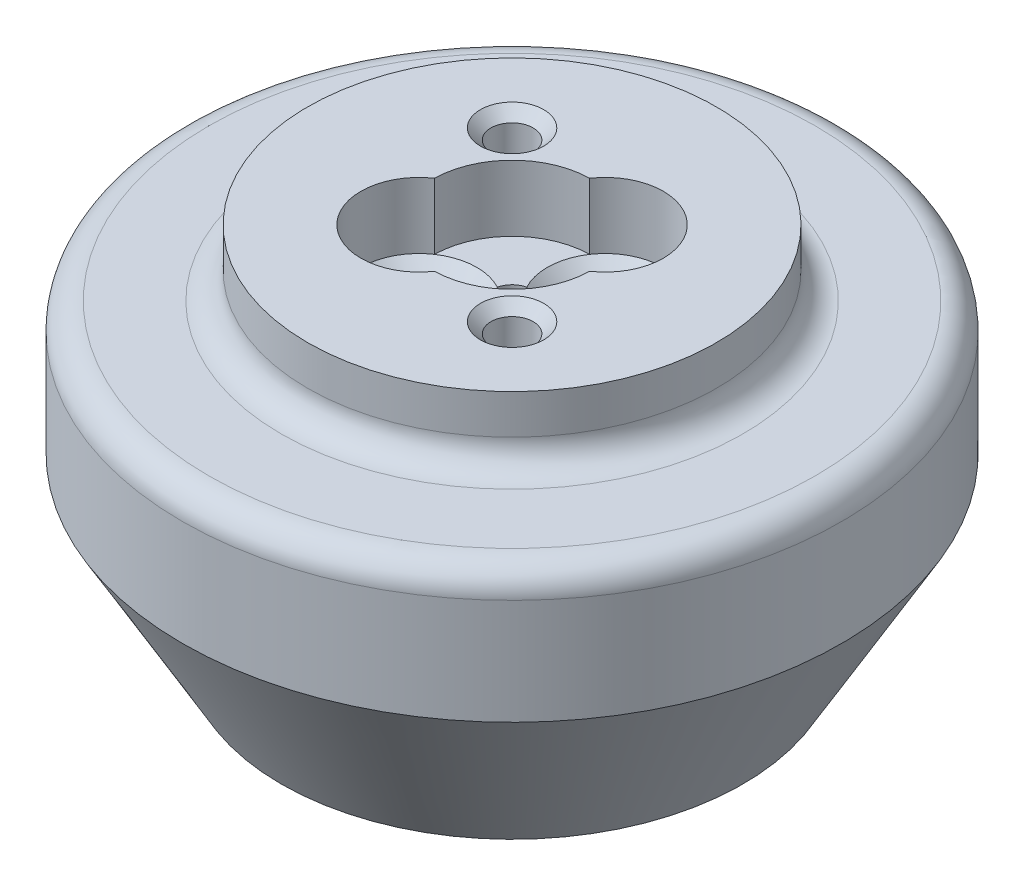
SolidWorks part; units mm, degrees
material "Brass"
ref_plane "Front" through (0, 0, 0) normal (0, 0, 1) x (1, 0, 0)
ref_plane "Top" through (0, 0, 0) normal (0, 1, 0) x (1, 0, 0)
ref_plane "Right" through (0, 0, 0) normal (1, 0, 0) x (0, 0, -1)
sketch "Sketch1" plane through (0, 0, 0) normal (0, 1, 0) x (1, 0, 0)
  circle A0 centre (0, 0) radius 7.1438
  circle A1 centre (0, 0) radius 12.5
  dimension "D1" = 14.2875
  dimension "D2" = 25
extrude "Boss-Extrude1" add sketch "Sketch1" along normal blind 10
sketch "Sketch2" plane through (0, 10, 0) normal (0, 1, 0) x (1, 0, 0)
  circle A0 centre (0, 0) radius 12.5 construction
  circle A1 centre (0, 0) radius 12.5
extrude "Boss-Extrude2" add sketch "Sketch2" along normal blind 1.5
chamfer "Chamfer1" distance 3.75 angle 60 1 edges at (0, 0, 12.5) first distance on face at (0, 0, 12.5)
sketch "Sketch8" plane through (0, 11.5, 0) normal (0, 1, 0) x (1, 0, 0)
  circle A1 centre (0, 0) radius 7.75
  circle A2 centre (0, 0) radius 3
  dimension "D1" = 6
  dimension "D2" = 15.5
extrude "Boss-Extrude3" add sketch "Sketch8" along normal blind 2.5
sketch "Sketch9" plane through (0, 11.5, 0) normal (0, 1, 0) x (1, 0, 0)
  circle A0 centre (1.7678, 1.7678) radius 0.7 construction
  circle A2 centre (-1.7678, -1.7678) radius 0.7 construction
  circle A4 centre (1.7678, 1.7678) radius 0.7 construction
  circle A6 centre (-1.7678, -1.7678) radius 0.7 construction
hole_wizard "CSK for M2 Flat Head Machine Screw1" positions "3DSketch2" profile "Sketch11" countersink size "M2" standard "ANSI Metric" end condition through all
sketch3d "3DSketch2"
  point P0 (-1.7678, 11.5, 1.7678)
  point P6 (1.7678, 11.5, -1.7678)
sketch "Sketch11" plane through (-1.7678, 11.5, 1.7678) normal (1, 0, 0) x (0, 0, 1)
  line L0 (0, 0) -> (0, 11.5)
  line L1 (0, 11.5) -> (1.2, 11.5)
  line L2 (1.2, 11.5) -> (1.2, 1)
  line L3 (1.2, 1) -> (2.2, 0)
  line L5 (2.2, 0) -> (0, 0)
  line L6 (-1.2, 1) -> (-2.2, 0) construction
  line L11 (0, -6.35) -> (0, 107.95) construction
  dimension "Thru Hole Dia." = 2.4
  dimension "Thru Hole Depth" = 11.5
  dimension "Near C'Sink Dia." = 4.4
  dimension "Near C'Sink Angle" = 90
sketch "Sketch16" plane through (0, 11.5, 0) normal (0, 1, 0) x (1, 0, 0)
  circle A0 centre (0, 0) radius 0.75
  dimension "D1" = 1.5
extrude "Cut-Extrude1" cut sketch "Sketch16" against normal through all
sketch "Sketch17" plane through (0, 14, 0) normal (0, 1, 0) x (1, 0, 0)
  circle A0 centre (3.182, -3.182) radius 0.7 construction
  circle A1 centre (-3.182, 3.182) radius 0.7 construction
  circle A2 centre (3.182, -3.182) radius 0.7
  circle A3 centre (-3.182, 3.182) radius 0.7
hole_wizard "M2x0.4 Tapped Hole1" positions "3DSketch4" profile "Sketch19" tap size "M2x0.4" standard "ANSI Metric" end condition through all
sketch3d "3DSketch4"
  point P0 (3.182, 14, 3.182)
  point P3 (-3.182, 14, -3.182)
sketch "Sketch19" plane through (3.182, 14, 3.182) normal (1, 0, 0) x (0, 0, 1)
  line L0 (0, 0) -> (0, 14)
  line L1 (0, 14) -> (0.8, 14)
  line L2 (0.8, 14) -> (0.8, 0.4)
  line L3 (0.8, 0.4) -> (1.2, 0)
  line L5 (1.2, 0) -> (0, 0)
  line L6 (-0.8, 0.4) -> (-1.2, 0) construction
  line L11 (0, -6.35) -> (0, 107.95) construction
  dimension "Thru Tap Drill Dia." = 1.6
  dimension "Thru Tap Drill Depth" = 14
  dimension "Near C'Sink Dia." = 2.4
  dimension "Near C'Sink Angle" = 90
cosmetic thread "Hole Thread3" parameters "D2"=2
cosmetic thread "Hole Thread4" parameters "D2"=2
sketch "Sketch20" plane through (0, 14, 0) normal (0, 1, 0) x (1, 0, 0)
  arc A4 (0.0551, -2.9995) -> (0.1721, -0.73) centre (-1.7678, -1.7678) ccw
  arc A5 (-0.73, 0.1721) -> (0.1721, -0.73) centre (0, 0) ccw
  arc A6 (-0.73, 0.1721) -> (-2.9995, 0.0551) centre (-1.7678, -1.7678) ccw
  arc A7 (-2.9995, 0.0551) -> (0.0551, -2.9995) centre (-1.7678, -1.7678) ccw
  arc A8 (0.0551, -2.9995) -> (0.1721, -0.73) centre (-1.7678, -1.7678) ccw
  arc A9 (-0.73, 0.1721) -> (0.1721, -0.73) centre (0, 0) ccw
  arc A10 (-0.73, 0.1721) -> (-2.9995, 0.0551) centre (-1.7678, -1.7678) ccw
  arc A11 (-2.9995, 0.0551) -> (0.0551, -2.9995) centre (-1.7678, -1.7678) ccw
  arc A12 (-0.0551, 2.9995) -> (-0.1721, 0.73) centre (1.7678, 1.7678) ccw
  arc A13 (0.73, -0.1721) -> (-0.1721, 0.73) centre (0, 0) ccw
  arc A14 (0.73, -0.1721) -> (2.9995, -0.0551) centre (1.7678, 1.7678) ccw
  arc A15 (2.9995, -0.0551) -> (-0.0551, 2.9995) centre (1.7678, 1.7678) ccw
  arc A16 (-0.0551, 2.9995) -> (-0.1721, 0.73) centre (1.7678, 1.7678) ccw
  arc A17 (0.73, -0.1721) -> (-0.1721, 0.73) centre (0, 0) ccw
  arc A18 (0.73, -0.1721) -> (2.9995, -0.0551) centre (1.7678, 1.7678) ccw
  arc A19 (2.9995, -0.0551) -> (-0.0551, 2.9995) centre (1.7678, 1.7678) ccw
  dimension "D1" = 0
  dimension "D2" = 0
extrude "Cut-Extrude2" cut sketch "Sketch20" against normal up to vertex (2.5 mm away) up to point (-2.9995, 11.5, -0.0551)
fillet "Fillet1" radius 1 2 edges at (0, 11.5, 7.75) (0, 11.5, 12.5)
